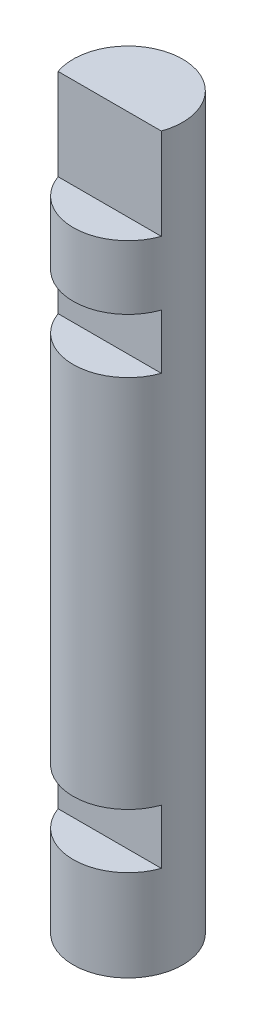
SolidWorks part; units mm, degrees
ref_plane "Alzado" through (0, 0, 0) normal (0, 0, 1) x (1, 0, 0)
ref_plane "Planta" through (0, 0, 0) normal (0, 1, 0) x (1, 0, 0)
ref_plane "Vista lateral" through (0, 0, 0) normal (1, 0, 0) x (0, 0, -1)
sketch "Croquis1" plane through (0, 0, 0) normal (0, 1, 0) x (1, 0, 0)
  circle A0 centre (0, 0) radius 3
  dimension "D1" = 6
extrude "Saliente-Extruir1" add sketch "Croquis1" along normal mid plane 40
sketch "Croquis3" plane through (0, 20, 0) normal (0, 1, 0) x (1, 0, 0)
  line L1 (-3.8744, -1) -> (4.3498, -1)
  line L2 (-3.8744, -1) -> (-3.8744, -3)
  line L3 (-3.8744, -3) -> (4.3498, -3)
  line L4 (4.3498, -1) -> (4.3498, -3)
  circle A0 centre (0, 0) radius 3 construction
  dimension "D1" = 2
  dimension "D2" = 1
extrude "Cortar-Extruir2" cut sketch "Croquis3" against normal blind 5 and the other way through all
sketch "Croquis4" plane through (0, 20, 0) normal (0, 1, 0) x (1, 0, 0)
  point P0 (0, 0)
ref_axis "Eje1" through (0, 20, 0) along (0, -1, 0)
sketch "Croquis8" plane through (0, 0, 1) normal (0, 0, 1) x (1, 0, 0)
  line L0 (-3, 20) -> (-3, -20) construction
  line L1 (-3, 11.5) -> (3, 11.5)
  line L2 (-3, 11.5) -> (-3, 8.5)
  line L3 (-3, 8.5) -> (3, 8.5)
  line L4 (3, 11.5) -> (3, 8.5)
  line L5 (3, -20) -> (3, 20) construction
  line L6 (2.8284, 15) -> (-2.8284, 15) construction
  line L7 (3, -20) -> (3, 20) construction
  line L8 (-3, -12) -> (3, -12)
  line L9 (-3, -12) -> (-3, -15)
  line L10 (-3, -15) -> (3, -15)
  line L11 (3, -12) -> (3, -15)
  line L12 (-3, -20) -> (3, -20) construction
  dimension "D1" = 3.5
  dimension "D2" = 3
  dimension "D3" = 5
  dimension "D4" = 3
extrude "Cortar-Extruir4" cut sketch "Croquis8" along normal blind 10
